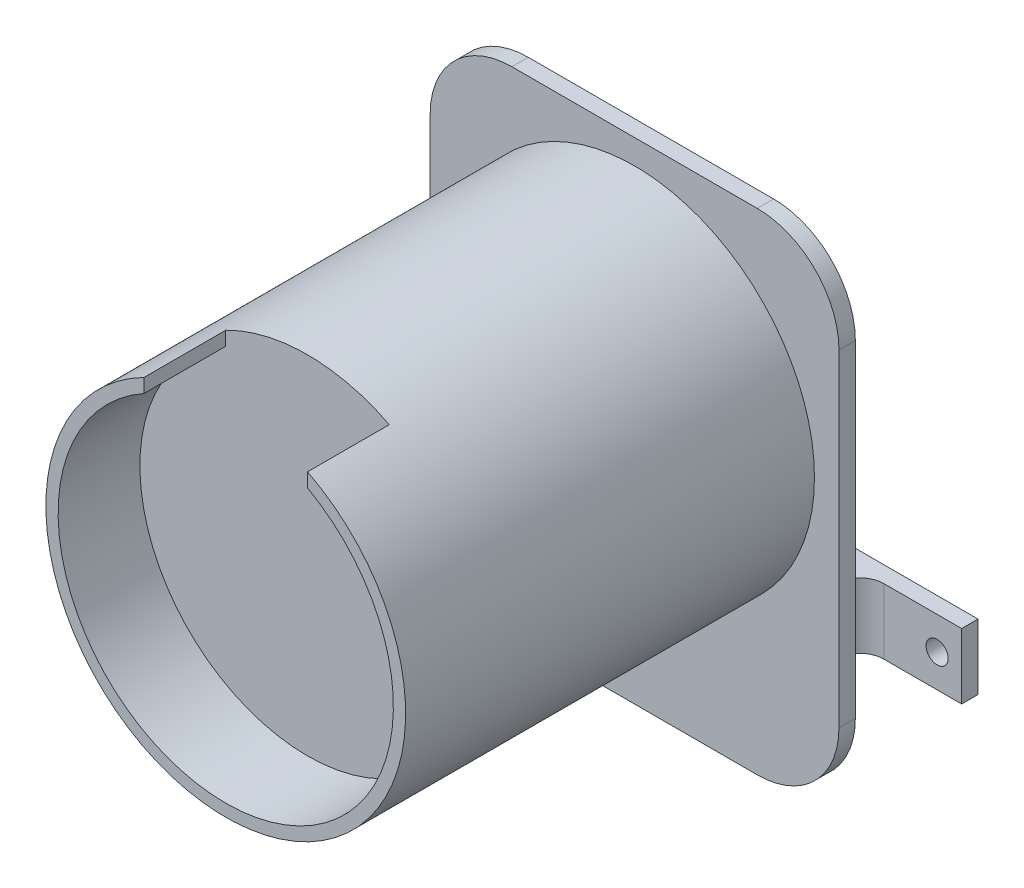
SolidWorks part; units mm, degrees
ref_plane "Front Plane" through (0, 0, 0) normal (0, 0, 1) x (1, 0, 0)
ref_plane "Top Plane" through (0, 0, 0) normal (0, 1, 0) x (1, 0, 0)
ref_plane "Right Plane" through (0, 0, 0) normal (1, 0, 0) x (0, 0, -1)
sketch "Sketch1" plane through (0, 0, 0) normal (0, 0, 1) x (1, 0, 0)
  line L0 (-20, 0) -> (20, 0) construction
  line L1 (-20, 4) -> (20, 4)
  line L2 (-20, 4) -> (-20, -4)
  line L3 (-20, -4) -> (20, -4)
  line L4 (20, 4) -> (20, -4)
  line L5 (-20, 4) -> (20, -4) construction
  line L6 (-20, -4) -> (20, 4) construction
  line L7 (0, 4) -> (0, -4) construction
  line L9 (-7.5, -4) -> (7.5, -4)
  line L10 (-7.5, -4) -> (-7.5, 4)
  line L11 (-7.5, 4) -> (7.5, 4)
  line L12 (7.5, -4) -> (7.5, 4)
  line L13 (-7.5, -4) -> (7.5, 4) construction
  line L14 (-7.5, 4) -> (7.5, -4) construction
  circle A0 centre (17, 0) radius 1.35
  circle A1 centre (-17, 0) radius 1.35
  point P0 (0, 0)
  point P12 (0, 0)
  dimension "D3" = 2.7
  dimension "D1" = 8
  dimension "D2" = 40
  dimension "D4" = 17
  dimension "D5" = 15
extrude "Boss-Extrude1" add sketch "Sketch1" along normal blind 2 contours L3 L10 L1 L2 A1 | L3 L12 L1 L10 | L12 L3 L4 L1 A0 region at (-13.5526, 0, 0) region at (0, 0, 0) region at (13.5526, 0, 0)
extrude "Boss-Extrude2" add sketch "Sketch1<3>" along normal blind 20 contours L3 L12 L1 L10 region at (0, 0, 0)
sketch "Sketch1<3>" plane through (0, 0, 0) normal (0, 0, 1) x (1, 0, 0) same geometry as "Sketch1"
sketch "Sketch2" plane through (0, 0, 20) normal (0, 0, 1) x (1, 0, 0)
  line L0 (-7.5, -4) -> (7.5, -4) construction
  line L1 (-25, 56) -> (25, 56)
  line L2 (-25, 56) -> (-25, -4)
  line L3 (-25, -4) -> (25, -4)
  line L4 (25, 56) -> (25, -4)
  point P6 (0, 56)
  dimension "D1" = 50
  dimension "D2" = 60
extrude "Boss-Extrude3" add sketch "Sketch2" along normal blind 2
sketch "Sketch3" plane through (0, 0, 22) normal (0, 0, 1) x (1, 0, 0)
  line L0 (0, 56) -> (0, -4) construction
  line L1 (25, 26) -> (-25, 26) construction
  line L4 (-25, 56) -> (-25, -4)
  line L5 (-25, -4) -> (25, -4)
  line L6 (25, -4) -> (25, 56)
  line L7 (25, 56) -> (-25, 56)
  line L8 (-25, 56) -> (-25, -4)
  line L9 (-25, -4) -> (25, -4)
  line L10 (25, -4) -> (25, 56)
  line L11 (25, 56) -> (-25, 56)
  circle A0 centre (0, 31) radius 22
  dimension "D2" = 44
  dimension "D3" = 25
  dimension "D1" = 0
extrude "Boss-Extrude4" add sketch "Sketch3" along normal blind 40 contours A0 region at (0, 31, 22)
sketch "Sketch5" plane through (0, 0, 62) normal (0, 0, 1) x (1, 0, 0)
  line L0 (-10, 50.5959) -> (10, 50.5959)
  line L1 (25, 56) -> (-25, 56) construction
  line L2 (-10, 50.5959) -> (-10, 48.8955)
  line L3 (10, 50.5959) -> (10, 48.8955)
  arc A0 (-10, 48.8955) -> (10, 48.8955) centre (0, 31) ccw
  circle A1 centre (0, 31) radius 22 construction
  circle A2 centre (0, 31) radius 22 construction
  circle M1 centre (0, 31) radius 22
  dimension "D1" = 41
  dimension "D2" = 20
extrude "Boss-Extrude5" add sketch "Sketch5" along normal blind 10 contours A0 L2 L3 M1 region at (-10.6055, 49.7457, 62)
fillet "Fillet1" radius 10 4 edges at (25, 56, 21) (-25, 56, 21) (-25, -4, 21) (25, -4, 21)
fillet "Fillet2" radius 12 2 edges at (7.5, 0, 20) (-7.5, 0, 20)
fillet "Fillet3" radius 3 2 edges at (7.5, 0, 2) (-7.5, 0, 2)
fillet "Fillet4" radius 22 1 edges at (0, 4, 20) curvature continuous yes second distance 5 first distance on face at (0, 22.0724, 20)
